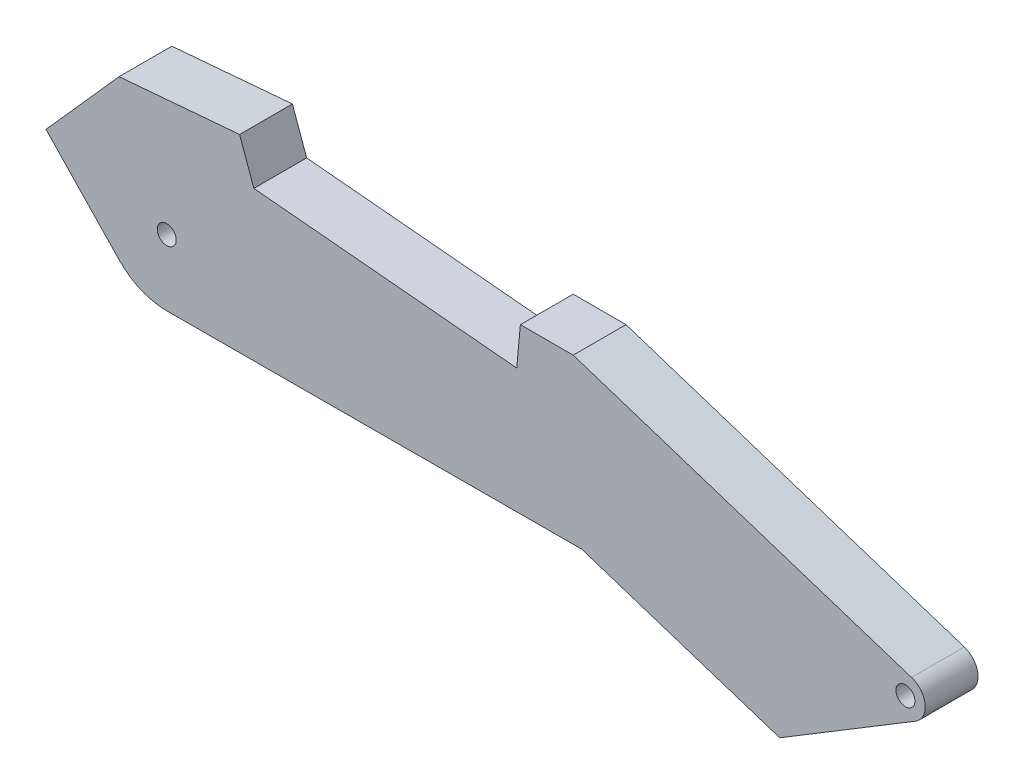
SolidWorks part; units mm, degrees
ref_plane "Front Plane" through (0, 0, 0) normal (0, 0, 1) x (1, 0, 0)
ref_plane "Top Plane" through (0, 0, 0) normal (0, 1, 0) x (1, 0, 0)
ref_plane "Right Plane" through (0, 0, 0) normal (1, 0, 0) x (0, 0, -1)
sketch "Sketch1" plane through (0, 0, 0) normal (0, 0, 1) x (1, 0, 0)
  line L1 (2.4683, -4.0729) -> (-30.2342, -23.8918)
  line L2 (-30.2342, -23.8918) -> (-77.8592, -8.412)
  line L3 (-160.1279, 36.83) -> (-189.129, 34.3616)
  line L4 (-189.129, 34.3616) -> (-206.6925, 14.605)
  line L5 (-206.6925, 14.605) -> (-189.129, -3.767)
  line L6 (-92.603, 30.979) -> (-93.4746, 21.494)
  line L7 (-177.6127, -8.672) -> (-77.8592, -8.412)
  line L8 (-93.4746, 21.494) -> (-156.7082, 27.305)
  line L9 (-156.7082, 27.305) -> (-160.1279, 36.83)
  line L10 (-92.603, 30.979) -> (-79.903, 30.979)
  line L11 (-79.903, 30.979) -> (-92.603, 30.979) construction
  line L12 (-79.903, 30.979) -> (1.4722, 4.5293)
  line L13 (1.4722, 4.5293) -> (-79.903, 30.979) construction
  circle A0 centre (0, 0) radius 2.286
  arc A1 (2.4683, -4.0729) -> (1.4722, 4.5293) centre (0, 0) ccw
  circle A2 centre (-177.654, 7.203) radius 2.286
  circle A3 centre (-177.654, 7.203) radius 25.4 construction
  arc A4 (-189.129, -3.767) -> (-177.6127, -8.672) centre (-177.654, 7.203) ccw
  arc A5 (-189.129, -3.767) -> (-177.6127, -8.672) centre (-177.654, 7.203) ccw construction
  point P17 (105.4504, -19.602)
  point P18 (-71.2573, 0.0759)
  point P19 (-77.8592, -8.412)
  point P20 (-177.654, -8.672)
  point P26 (-189.129, -3.767)
  point P28 (-30.2342, -23.8918)
  point P29 (2.4683, -4.0729)
  point P31 (0, 5.0078)
  point P37 (-92.603, 30.979)
  point P46 (0, 0)
  point P47 (0, 0)
  dimension "D1" = 4.572
extrude "Boss-Extrude1" add sketch "Sketch1" along normal blind 12.7
